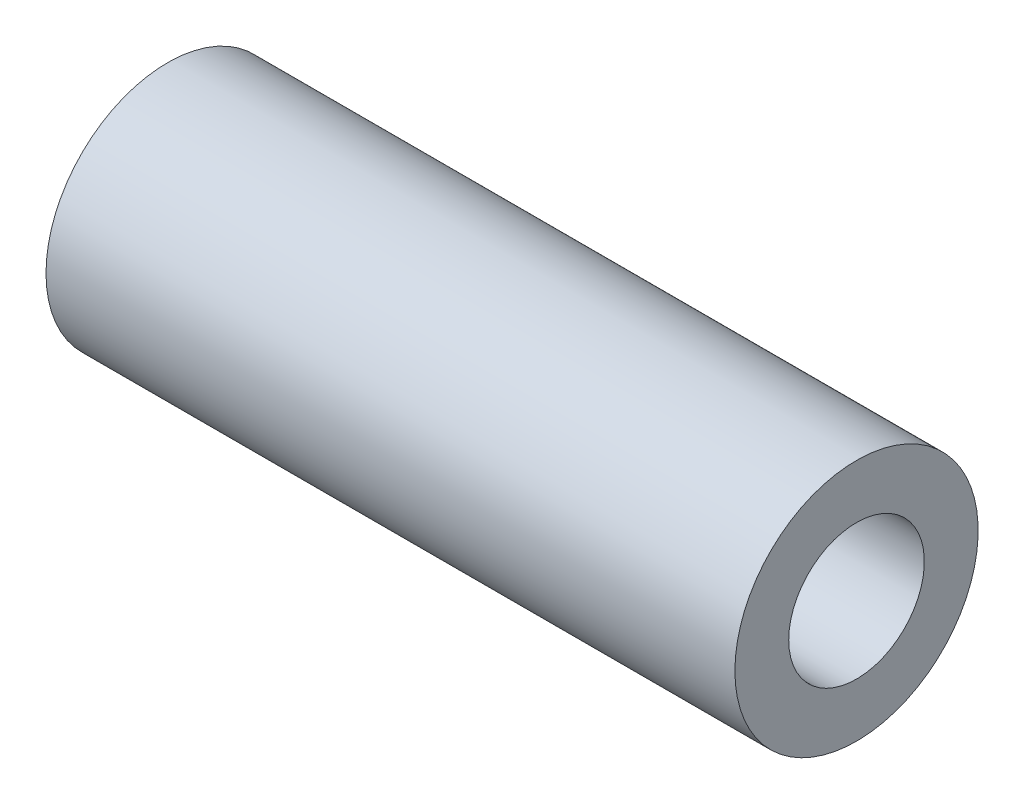
SolidWorks part; units mm, degrees
material "Silicon Rubber"
ref_plane "X-Y Datum" through (0, 0, 0) normal (0, 0, 1) x (1, 0, 0)
ref_plane "X-Z Datum" through (0, 0, 0) normal (0, 1, 0) x (1, 0, 0)
ref_plane "Y-Z Datum" through (0, 0, 0) normal (1, 0, 0) x (0, 0, -1)
sketch "Sketch1" plane through (0, 0, 0) normal (0, 1, 0) x (1, 0, 0)
  line L0 (0, 0) -> (-50.8, 0)
  point P3 (-37.7805, 4.924)
  point P4 (-38.1, 0)
  point P5 (0, 0)
  dimension "D1" = 50.8
sweep "Sweep1" add path "Sketch1" circular profile diameter 17.9375 parameters "D3"=17.9375
sweep "Cut-Sweep1" cut path "Sketch1<3>" circular profile diameter 10 parameters "D3"=10
sketch "Sketch1<3>" plane through (0, 0, 0) normal (0, 1, 0) x (1, 0, 0) same geometry as "Sketch1"
